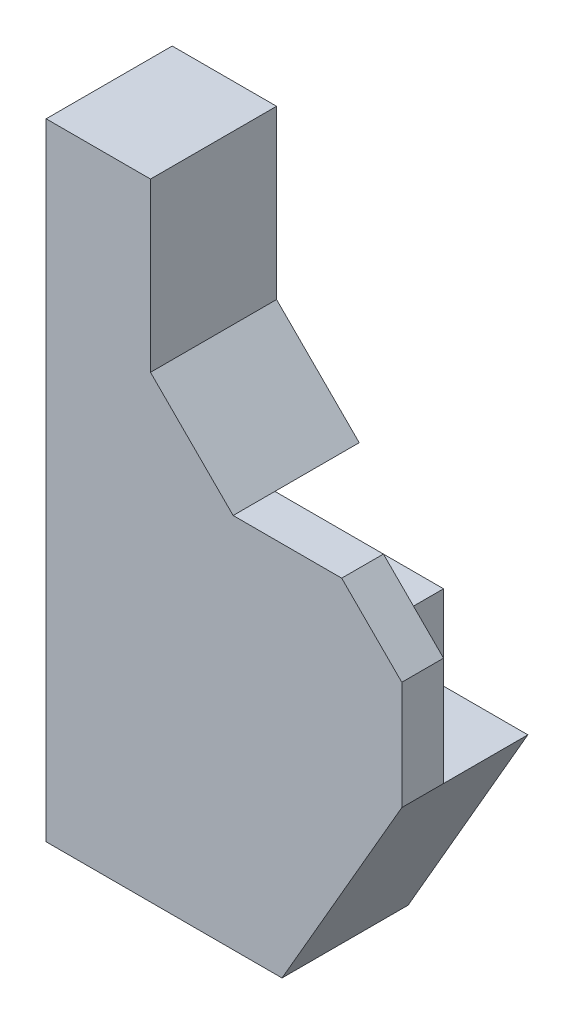
SolidWorks part; units mm, degrees
material "6063-T5"
ref_plane "Front Plane" through (0, 0, 0) normal (0, 0, 1) x (1, 0, 0)
ref_plane "Top Plane" through (0, 0, 0) normal (0, 1, 0) x (1, 0, 0)
ref_plane "Right Plane" through (0, 0, 0) normal (1, 0, 0) x (0, 0, -1)
sketch "Sketch1" plane through (0, 0, 0) normal (0, 0, 1) x (1, 0, 0)
  line L0 (0, 0) -> (0, 150)
  line L1 (0, 150) -> (25, 150)
  line L2 (25, 150) -> (25, 109.9)
  line L5 (85.2, 49.7) -> (56.5057, 0)
  line L6 (56.5057, 0) -> (0, 0)
  line L10 (85.2, 49.7) -> (65, 49.7)
  line L11 (65, 49.7) -> (65, 69.9)
  line L15 (5, 90.1) -> (44.8, 90.1)
  line L16 (22.8458, 10) -> (22.8458, 0) construction
  line L17 (5, 80) -> (0, 80) construction
  line L18 (51.2366, 10.8736) -> (59.8968, 5.8736) construction
  line L22 (65, 69.9) -> (5, 69.9)
  line L23 (5, 90.1) -> (5, 69.9)
  line L30 (55, 52.3) -> (65, 52.3) construction
  line L31 (67.8795, 49.7) -> (67.8795, 39.7) construction
  line L33 (10, 64.9) -> (10, 10)
  line L34 (10, 10) -> (50.7322, 10)
  line L35 (50.7322, 10) -> (67.8795, 39.7)
  line L36 (67.8795, 39.7) -> (55, 39.7)
  line L37 (55, 39.7) -> (55, 64.9)
  line L38 (55, 64.9) -> (10, 64.9)
  line L39 (10, 37.45) -> (0, 37.45) construction
  line L40 (32.5, 64.9) -> (32.5, 69.9) construction
  line L41 (25, 109.9) -> (44.8, 90.1)
  point P5 (3, 61.6207)
  point P14 (3, 56.8851)
  point P15 (48.6824, 70.1)
  point P16 (0, 0)
  point P21 (74.4929, 26.7)
  point P22 (65.7007, 44.3428)
  point P25 (75.1, 49.7)
  point P26 (67.3961, 49.7)
  point P34 (66.2197, 44.7)
  dimension "D1" = 45
  dimension "D2" = 60
  dimension "D3" = 20.2
  dimension "D4" = 20.2
  dimension "D5" = 5
  dimension "D6" = 80
  dimension "D7" = 60
  dimension "D8" = 25
  dimension "D9" = 150
  dimension "D10" = 20.2
  dimension "D11" = 69.9
  dimension "D12" = 10
extrude "Boss-Extrude1" add sketch "Sketch1" along normal blind 10.1 and the other way blind 10.1
sketch "Sketch2" plane through (0, 0, 10.1) normal (0, 0, 1) x (1, 0, 0)
  line L11 (44.8, 90.1) -> (70.8, 90.1)
  line L12 (70.8, 90.1) -> (85.2, 75.7)
  line L13 (85.2, 75.7) -> (85.2, 49.7)
  line L22 (0, 0) -> (56.5057, 0)
  line L23 (56.5057, 0) -> (85.2, 49.7)
  line L24 (85.2, 49.7) -> (65, 49.7)
  line L25 (65, 49.7) -> (65, 69.9)
  line L26 (65, 69.9) -> (5, 69.9)
  line L27 (5, 69.9) -> (5, 90.1)
  line L28 (5, 90.1) -> (44.8, 90.1)
  line L29 (44.8, 90.1) -> (25, 109.9)
  line L30 (25, 109.9) -> (25, 150)
  line L31 (25, 150) -> (0, 150)
  line L32 (0, 150) -> (0, 0)
  line L33 (0, 0) -> (56.5057, 0)
  line L34 (56.5057, 0) -> (85.2, 49.7)
  line L40 (44.8, 90.1) -> (25, 109.9)
  line L41 (25, 109.9) -> (25, 150)
  line L42 (25, 150) -> (0, 150)
  line L43 (0, 150) -> (0, 0)
  dimension "D2" = 135
  dimension "D3" = 26
  dimension "D1" = 0
extrude "Boss-Extrude2" add sketch "Sketch2" along normal blind 10
